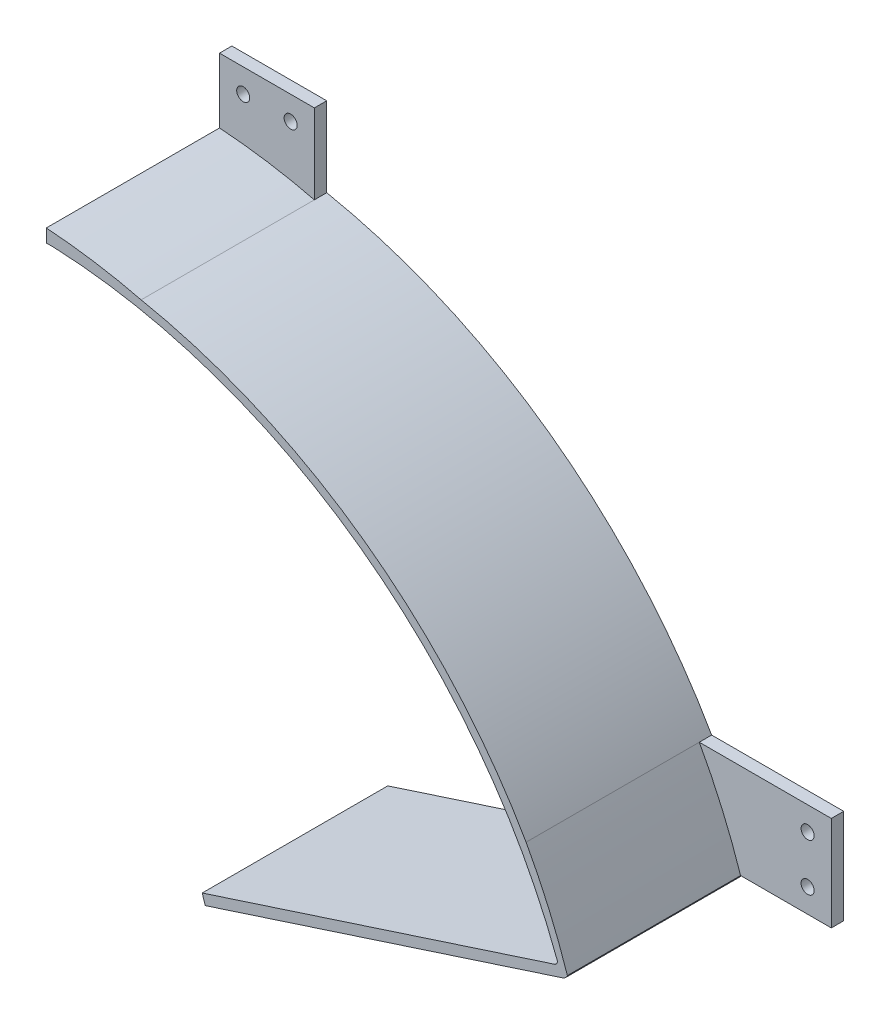
SolidWorks part; units mm, degrees
ref_plane "정면" through (0, 0, 0) normal (0, 0, 1) x (1, 0, 0)
ref_plane "윗면" through (0, 0, 0) normal (0, 1, 0) x (1, 0, 0)
ref_plane "우측면" through (0, 0, 0) normal (1, 0, 0) x (0, 0, -1)
sketch "스케치1" plane through (0, 0, 0) normal (0, 0, 1) x (1, 0, 0)
  line L0 (-161.9097, -132.696) -> (-19.2512, -86.3435)
  line L1 (-225.3913, 64.758) -> (-225.3913, 96.2152)
  line L2 (-187.0548, 96.2152) -> (-187.0548, 62.0316)
  line L3 (-19.2512, -86.3435) -> (21.8794, -86.3435)
  line L4 (21.8794, -48.0069) -> (-33.7387, -48.0069)
  line L5 (12.2953, -48.0069) -> (12.2953, -86.3435) construction
  line L6 (-187.0548, 86.6311) -> (-225.3913, 86.6311) construction
  line L7 (-225.3913, 96.2152) -> (-187.0548, 96.2152)
  line L8 (21.8794, -48.0069) -> (21.8794, -86.3435)
  line L9 (-19.9154, -84.9469) -> (-162.3836, -131.2376)
  line L10 (-225.3913, 64.758) -> (-222.2581, 64.758)
  line L11 (-162.3836, -131.2376) -> (-161.9097, -132.696)
  circle A0 centre (-215.8072, 86.6311) radius 2.6356
  circle A1 centre (-196.6389, 86.6311) radius 2.6356
  circle A2 centre (12.2953, -76.7594) radius 2.6356
  circle A3 centre (12.2953, -57.5911) radius 2.6356
  arc A5 (-33.7387, -48.0069) -> (-187.0548, 62.0316) centre (-232.1002, -162.5565) ccw
  arc A7 (-19.9154, -84.9469) -> (-18.9527, -82.952) centre (-20.3893, -83.4885) ccw
  arc A8 (-18.9527, -82.952) -> (-222.2581, 64.758) centre (-232.1002, -162.5565) ccw
  dimension "D1" = 150
extrude "보스-돌출1" add sketch "스케치1" along normal blind 5
sketch "스케치2" plane through (0, 0, 5) normal (0, 0, 1) x (1, 0, 0)
  line L10 (-19.2512, -86.3435) -> (21.8794, -86.3435)
  line L11 (21.8794, -86.3435) -> (21.8794, -48.0069)
  line L12 (21.8794, -48.0069) -> (-33.7387, -48.0069)
  line L13 (-187.0548, 62.0316) -> (-187.0548, 96.2152)
  line L14 (-187.0548, 96.2152) -> (-225.3913, 96.2152)
  line L15 (-225.3913, 96.2152) -> (-225.3913, 64.758)
  line L16 (-225.3913, 64.758) -> (-222.2581, 64.758)
  line L17 (-19.9154, -84.9469) -> (-162.3836, -131.2376)
  line L18 (-162.3836, -131.2376) -> (-161.9097, -132.696)
  line L19 (-161.9097, -132.696) -> (-19.2512, -86.3435)
  line L20 (-19.2512, -86.3435) -> (21.8794, -86.3435)
  line L21 (21.8794, -86.3435) -> (21.8794, -48.0069)
  line L22 (21.8794, -48.0069) -> (-33.7387, -48.0069)
  line L23 (-187.0548, 62.0316) -> (-187.0548, 96.2152)
  line L24 (-187.0548, 96.2152) -> (-225.3913, 96.2152)
  line L25 (-225.3913, 96.2152) -> (-225.3913, 64.758)
  line L26 (-225.3913, 64.758) -> (-222.2581, 64.758)
  line L27 (-19.9154, -84.9469) -> (-162.3836, -131.2376)
  line L28 (-162.3836, -131.2376) -> (-161.9097, -132.696)
  line L29 (-161.9097, -132.696) -> (-19.2512, -86.3435)
  circle A0 centre (-232.1002, -162.5565) radius 229.0609
  circle A1 centre (-232.1002, -162.5565) radius 227.5274
  arc A3 (-33.7387, -48.0069) -> (-187.0548, 62.0316) centre (-232.1002, -162.5565) ccw
  arc A4 (-18.9527, -82.952) -> (-222.2581, 64.758) centre (-232.1002, -162.5565) ccw
  arc A5 (-19.9154, -84.9469) -> (-18.9527, -82.952) centre (-20.3893, -83.4885) ccw
  arc A6 (-33.7387, -48.0069) -> (-187.0548, 62.0316) centre (-232.1002, -162.5565) ccw
  arc A7 (-18.9527, -82.952) -> (-222.2581, 64.758) centre (-232.1002, -162.5565) ccw
  arc A8 (-19.9154, -84.9469) -> (-18.9527, -82.952) centre (-20.3893, -83.4885) ccw
  line M16 (-19.2512, -86.3435) -> (21.8794, -86.3435)
  arc M19 (-33.7387, -48.0069) -> (-187.0548, 62.0316) centre (-232.1002, -162.5565) ccw
  arc M24 (-222.2581, 64.758) -> (-18.9527, -82.952) centre (-232.1002, -162.5565) cw
  arc M25 (-18.9527, -82.952) -> (-19.9154, -84.9469) centre (-20.3893, -83.4885) cw
  line M26 (-19.9154, -84.9469) -> (-162.3836, -131.2376)
  line M27 (-162.3836, -131.2376) -> (-161.9097, -132.696)
  line M28 (-161.9097, -132.696) -> (-19.2512, -86.3435)
  dimension "D1" = 0
extrude "보스-돌출2" add sketch "스케치2" against normal blind 50 contours A1 M16 M25 M26 M27 M28 | A1 L20 A0 L25 M19 M24 region at (-89.866, -108.4801, 5) region at (-18.0845, -84.5566, 5)
fillet "필렛1" radius 3 1 edges at (-16.0899, -86.3435, -22.5)
sketch "스케치3" plane through (0, 0, 5) normal (0, 0, 1) x (1, 0, 0)
  line L0 (-161.9097, -132.696) -> (-161.1475, -135.0419)
  line L1 (-161.1475, -135.0419) -> (-13.7338, -87.1442)
  line L10 (-225.3913, 96.2152) -> (-225.3913, 64.758)
  line L11 (-225.3913, 64.758) -> (-222.2581, 64.758)
  line L12 (-19.9154, -84.9469) -> (-162.3836, -131.2376)
  line L13 (-162.3836, -131.2376) -> (-161.9097, -132.696)
  line L14 (-161.9097, -132.696) -> (-19.2512, -86.3435)
  line L15 (-19.2512, -86.3435) -> (21.8794, -86.3435)
  line L16 (21.8794, -86.3435) -> (21.8794, -48.0069)
  line L17 (21.8794, -48.0069) -> (-33.7387, -48.0069)
  line L18 (-187.0548, 62.0316) -> (-187.0548, 96.2152)
  line L19 (-187.0548, 96.2152) -> (-225.3913, 96.2152)
  line L20 (-225.3913, 96.2152) -> (-225.3913, 64.758)
  line L21 (-225.3913, 64.758) -> (-222.2581, 64.758)
  line L22 (-19.9154, -84.9469) -> (-162.3836, -131.2376)
  line L23 (-162.3836, -131.2376) -> (-161.9097, -132.696)
  line L24 (-161.9097, -132.696) -> (-19.2512, -86.3435)
  line L25 (-19.2512, -86.3435) -> (21.8794, -86.3435)
  line L26 (21.8794, -86.3435) -> (21.8794, -48.0069)
  line L27 (21.8794, -48.0069) -> (-33.7387, -48.0069)
  line L28 (-187.0548, 62.0316) -> (-187.0548, 96.2152)
  line L29 (-187.0548, 96.2152) -> (-225.3913, 96.2152)
  circle A0 centre (-232.1002, -162.5565) radius 231.0214
  arc A3 (-18.9527, -82.952) -> (-222.2581, 64.758) centre (-232.1002, -162.5565) ccw
  arc A4 (-19.9154, -84.9469) -> (-18.9527, -82.952) centre (-20.3893, -83.4885) ccw
  arc A5 (-33.7387, -48.0069) -> (-187.0548, 62.0316) centre (-232.1002, -162.5565) ccw
  arc A6 (-18.9527, -82.952) -> (-222.2581, 64.758) centre (-232.1002, -162.5565) ccw
  arc A7 (-19.9154, -84.9469) -> (-18.9527, -82.952) centre (-20.3893, -83.4885) ccw
  arc A8 (-33.7387, -48.0069) -> (-187.0548, 62.0316) centre (-232.1002, -162.5565) ccw
  line M17 (-225.3913, 64.758) -> (-222.2581, 64.758)
  arc M18 (-222.2581, 64.758) -> (-18.9527, -82.952) centre (-232.1002, -162.5565) cw
  arc M19 (-18.9527, -82.952) -> (-19.9154, -84.9469) centre (-20.3893, -83.4885) cw
  line M20 (-19.9154, -84.9469) -> (-162.3836, -131.2376)
  line M21 (-162.3836, -131.2376) -> (-161.9097, -132.696)
  line M22 (-161.9097, -132.696) -> (-19.2512, -86.3435)
  line M23 (-19.2512, -86.3435) -> (21.8794, -86.3435)
  arc M26 (-33.7387, -48.0069) -> (-187.0548, 62.0316) centre (-232.1002, -162.5565) ccw
  line M27 (-187.0548, 62.0316) -> (-187.0548, 96.2152)
  dimension "D2" = 155
  dimension "D3" = 4
  dimension "D1" = 0
extrude "보스-돌출3" add sketch "스케치3" against normal blind 70 contours L1 A0 L0 M23 M22 | L27 A0 M27 M26 | A0 L27 L20 M23 M26 M27 M17 M18 M19 M20 M21 M22 region at (-88.5952, -110.1793, 5) region at (-159.3721, -131.0653, 5) region at (-32.6083, -46.0897, 5)
fillet "필렛2" radius 3 1 edges at (-13.7338, -87.1442, -30)
sketch "스케치4" plane through (0, 0, 5) normal (0, 0, 1) x (1, 0, 0)
  line L10 (-14.796, -86.3435) -> (21.8794, -86.3435)
  line L11 (21.8794, -86.3435) -> (21.8794, -48.0069)
  line L12 (21.8794, -48.0069) -> (-31.4779, -48.0069)
  line L13 (-187.0548, 64.0309) -> (-187.0548, 96.2152)
  line L14 (-187.0548, 96.2152) -> (-225.3913, 96.2152)
  line L15 (-225.3913, 96.2152) -> (-225.3913, 64.758)
  line L16 (-225.3913, 64.758) -> (-222.2581, 64.758)
  line L17 (-19.9154, -84.9469) -> (-162.3836, -131.2376)
  line L18 (-162.3836, -131.2376) -> (-161.1475, -135.0419)
  line L19 (-161.1475, -135.0419) -> (-16.6593, -88.0948)
  line L20 (-14.796, -86.3435) -> (21.8794, -86.3435)
  line L21 (21.8794, -86.3435) -> (21.8794, -48.0069)
  line L22 (21.8794, -48.0069) -> (-31.4779, -48.0069)
  line L23 (-187.0548, 64.0309) -> (-187.0548, 96.2152)
  line L24 (-187.0548, 96.2152) -> (-225.3913, 96.2152)
  line L25 (-225.3913, 96.2152) -> (-225.3913, 64.758)
  line L26 (-225.3913, 64.758) -> (-222.2581, 64.758)
  line L27 (-19.9154, -84.9469) -> (-162.3836, -131.2376)
  line L28 (-162.3836, -131.2376) -> (-161.1475, -135.0419)
  line L29 (-161.1475, -135.0419) -> (-16.6593, -88.0948)
  arc A0 (-225.3913, 70.0323) -> (-187.0548, 64.0309) centre (-241.2847, -156.9394) cw
  arc A1 (-31.4779, -48.0069) -> (-14.796, -86.3435) centre (-230.8857, -157.5755) cw
  arc A4 (-16.6593, -88.0948) -> (-14.796, -86.3435) centre (-17.5863, -85.2416) ccw
  arc A5 (-31.4779, -48.0069) -> (-187.0548, 64.0309) centre (-232.1002, -162.5565) ccw
  arc A6 (-18.9527, -82.952) -> (-222.2581, 64.758) centre (-232.1002, -162.5565) ccw
  arc A7 (-19.9154, -84.9469) -> (-18.9527, -82.952) centre (-20.3893, -83.4885) ccw
  arc A8 (-16.6593, -88.0948) -> (-14.796, -86.3435) centre (-17.5863, -85.2416) ccw
  arc A9 (-31.4779, -48.0069) -> (-187.0548, 64.0309) centre (-232.1002, -162.5565) ccw
  arc A10 (-18.9527, -82.952) -> (-222.2581, 64.758) centre (-232.1002, -162.5565) ccw
  arc A11 (-19.9154, -84.9469) -> (-18.9527, -82.952) centre (-20.3893, -83.4885) ccw
  arc M15 (-16.6593, -88.0948) -> (-14.796, -86.3435) centre (-17.5863, -85.2416) ccw
  arc M19 (-31.4779, -48.0069) -> (-187.0548, 64.0309) centre (-232.1002, -162.5565) ccw
  line M23 (-225.3913, 64.758) -> (-222.2581, 64.758)
  arc M24 (-222.2581, 64.758) -> (-18.9527, -82.952) centre (-232.1002, -162.5565) cw
  arc M25 (-18.9527, -82.952) -> (-19.9154, -84.9469) centre (-20.3893, -83.4885) cw
  line M26 (-19.9154, -84.9469) -> (-162.3836, -131.2376)
  line M27 (-162.3836, -131.2376) -> (-161.1475, -135.0419)
  line M28 (-161.1475, -135.0419) -> (-16.6593, -88.0948)
  dimension "D1" = 0
extrude "보스-돌출4" add sketch "스케치4" along normal blind 70 contours A1 A0 L25 M19 M23 M24 M25 M26 M27 M28 M15 region at (-17.5449, -85.2857, 5)
sketch "스케치5" plane through (-225.3913, 0, 0) normal (-1, 0, 0) x (0, 0, 1)
  line L1 (0, 68.3676) -> (-89.0633, 68.3676)
  line L2 (0, 68.3676) -> (0, -226.9567)
  line L3 (0, -226.9567) -> (-89.0633, -226.9567)
  line L4 (-89.0633, 68.3676) -> (-89.0633, -226.9567)
extrude "컷-돌출1" cut sketch "스케치5" against normal blind 275
